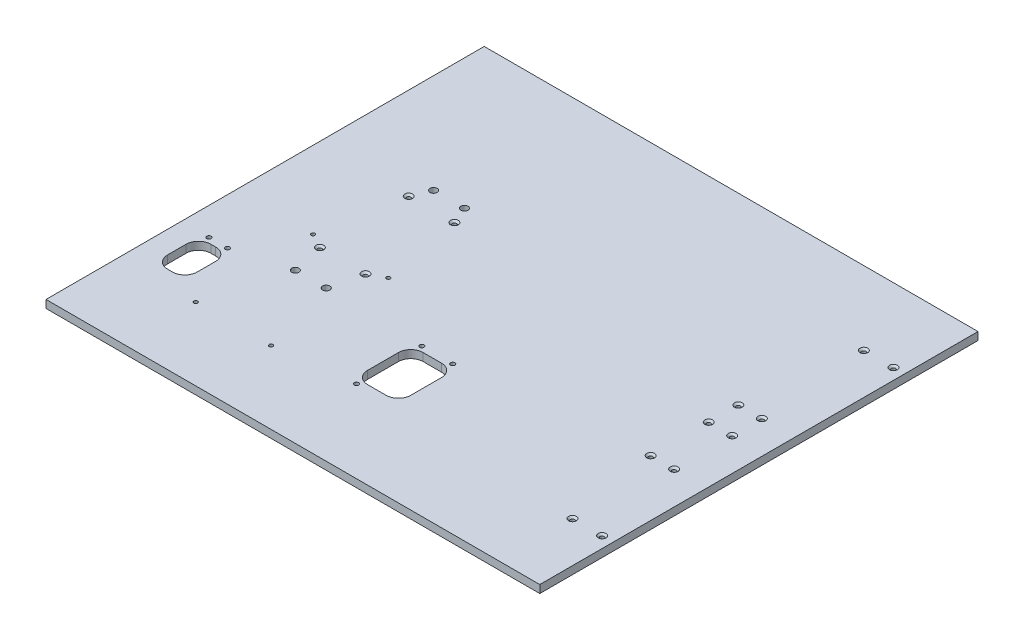
SolidWorks part; units mm, degrees
material "6061-T6 (SS)"
ref_plane "Front Plane" through (0, 0, 0) normal (0, 0, 1) x (1, 0, 0)
ref_plane "Top Plane" through (0, 0, 0) normal (0, 1, 0) x (1, 0, 0)
ref_plane "Right Plane" through (0, 0, 0) normal (1, 0, 0) x (0, 0, -1)
sketch "Sketch1" plane through (0, 0, 0) normal (1, 0, 0) x (0, 0, -1)
  line L1 (-177.5, 0) -> (177.5, 0)
  line L2 (-177.5, -6.35) -> (-177.5, 0)
  line L4 (177.5, -6.35) -> (177.5, 0)
  line L7 (-177.5, -6.35) -> (177.5, -6.35)
  dimension "D1" = 355
  dimension "D2" = 6.35
extrude "Boss-Extrude1" add sketch "Sketch1" along normal mid plane 400
sketch "Sketch9" plane through (0, 0, 0) normal (0, 1, 0) x (1, 0, 0)
  line L4 (200, 0) -> (-200, 0) construction
  line L5 (200, 177.5) -> (200, -177.5) construction
  line L6 (-200, 177.5) -> (-200, -177.5) construction
  line L7 (-125.5, 41.85) -> (-88.5, 41.85) construction
  line L8 (-88.5, 41.85) -> (-88.5, -30.15) construction
  line L9 (-88.5, -30.15) -> (-125.5, -30.15) construction
  line L10 (-125.5, -30.15) -> (-125.5, 41.85) construction
  line L11 (154.5, 28.85) -> (154.5, 4.85) construction
  line L12 (154.5, 4.85) -> (154.5, -42.15) construction
  line L13 (154.5, -42.15) -> (173.5, -42.15) construction
  line L14 (173.5, -42.15) -> (173.5, 4.85) construction
  line L15 (173.5, 4.85) -> (173.5, 28.85) construction
  line L16 (173.5, 28.85) -> (154.5, 28.85) construction
  line L17 (173.5, 4.85) -> (154.5, 4.85) construction
  circle A8 centre (-125.5, 41.85) radius 1.5
  circle A9 centre (-88.5, 41.85) radius 1.5
  circle A10 centre (-125.5, -30.15) radius 1.5
  circle A11 centre (-88.5, -30.15) radius 1.5
  circle A12 centre (154.5, 28.85) radius 1.5
  circle A13 centre (173.5, 4.85) radius 1.5
  circle A14 centre (154.5, 4.85) radius 1.5
  circle A15 centre (173.5, 28.85) radius 1.5
  circle A16 centre (154.5, -42.15) radius 1.5
  circle A17 centre (173.5, -42.15) radius 1.5
  dimension "D1" = 41.85
  dimension "D2" = 72
  dimension "D3" = 37
  dimension "D4" = 74.5
  dimension "D5" = 4.85
  dimension "D6" = 24
  dimension "D7" = 71
  dimension "D8" = 19
  dimension "D9" = 243
extrude "Cut-Extrude8" cut sketch "Sketch9" against normal blind 10
sketch "Sketch19" plane through (0, 0, 0) normal (0, 1, 0) x (1, 0, 0)
  circle A0 centre (-137.5, -23.7) radius 1.5
  circle A2 centre (-76.5, -23.7) radius 1.5
  circle A4 centre (-76.5, -118.7) radius 1.5
  circle A9 centre (-137.5, -118.7) radius 1.5
  dimension "D1" = 3
extrude "Cut-Extrude9" cut sketch "Sketch19" against normal blind 10
hole_wizard "CSK for M3 Flat Head Machine Screw3" positions "Sketch27" profile "Sketch26" countersink size "M3" standard "Ansi Metric"
sketch "Sketch27" plane through (0, 0, 0) normal (0, 1, 0) x (-1, 0, 0)
  point P0 (88.5, -41.85)
  point P7 (125.5, -41.85)
  point P10 (125.5, 30.15)
  point P13 (88.5, 30.15)
  point P22 (-167, 118)
  point P25 (-191, 118)
  point P28 (-154.5, 42.15)
  point P31 (-173.5, 42.15)
  point P34 (-173.5, -4.85)
  point P37 (-154.5, -4.85)
  point P40 (-173.5, -28.85)
  point P43 (-154.5, -28.85)
  point P46 (-191, -118)
  point P49 (-167, -118)
sketch "Sketch26" plane through (-88.5, 0, -41.85) normal (1, 0, 0) x (0, 0, 1)
  line L0 (0, 0) -> (0, 11.0215)
  line L1 (0, 11.0215) -> (1.7, 10)
  line L2 (1.7, 10) -> (1.7, 1.45)
  line L3 (1.7, 1.45) -> (3.15, 0)
  line L5 (3.15, 0) -> (0, 0)
  line L6 (-1.7, 1.45) -> (-3.15, 0) construction
  line L10 (0, 11.0215) -> (-1.7, 10) construction
  line L11 (0, -6.35) -> (0, 107.95) construction
  dimension "Hole Dia." = 3.4
  dimension "Hole Depth" = 10
  dimension "Near C'Sink Dia." = 6.3
  dimension "Near C'Sink Angle" = 90
  dimension "Drill Angle" = 118
sketch "Sketch28" plane through (0, 0, 0) normal (0, 1, 0) x (-1, 0, 0)
  line L1 (10, 62) -> (-5, 62)
  line L2 (20, 72) -> (20, 97)
  line L3 (10, 107) -> (-5, 107)
  line L4 (-15, 72) -> (-15, 97)
  line L5 (200, -177.5) -> (200, 177.5) construction
  line L6 (162.5, 68) -> (177.5, 68) construction
  line L7 (168, 107) -> (172, 107)
  line L8 (158, 97) -> (158, 82)
  line L9 (168, 72) -> (172, 72)
  line L10 (182, 97) -> (182, 82)
  line L11 (170, 68) -> (170, 72) construction
  arc A0 (-5, 107) -> (-15, 97) centre (-5, 97) ccw
  arc A1 (-5, 62) -> (-15, 72) centre (-5, 72) cw
  arc A2 (10, 62) -> (20, 72) centre (10, 72) ccw
  arc A3 (20, 97) -> (10, 107) centre (10, 97) ccw
  circle A4 centre (15, 111) radius 1.75
  arc A5 (172, 72) -> (182, 82) centre (172, 82) ccw
  arc A6 (158, 82) -> (168, 72) centre (168, 82) ccw
  arc A7 (168, 107) -> (158, 97) centre (168, 97) ccw
  arc A8 (172, 107) -> (182, 97) centre (172, 97) cw
  circle A9 centre (15, 58) radius 1.75
  circle A10 centre (-10, 58) radius 1.75
  circle A11 centre (162.5, 68) radius 1.75
  circle A12 centre (177.5, 68) radius 1.75
  dimension "D5" = 10
  dimension "D6" = 4
  dimension "D8" = 5
  dimension "D9" = 10
  dimension "D14" = 3.5
  dimension "D2" = 45
  dimension "D3" = 180
  dimension "D4" = 215
  dimension "D7" = 4
  dimension "D10" = 18
  dimension "D12" = 24
  dimension "D13" = 35
  dimension "D15" = 5
  dimension "D16" = 15
  dimension "D17" = 4
extrude "Cut-Extrude11" cut sketch "Sketch28" against normal blind 10
hole_wizard "M5 Clearance Hole1" positions "Sketch32" profile "Sketch29" hole size "M5" standard "ANSI Metric" end condition through all
sketch "Sketch32" plane through (0, 0, 0) normal (0, 1, 0) x (1, 0, 0)
  line L0 (-200, 0) -> (200, 0) construction
  line L1 (-200, 177.5) -> (-200, -177.5) construction
  line L2 (200, 177.5) -> (200, -177.5) construction
  line L4 (-94.5, 56) -> (-94.5, -56) construction
  line L5 (-94.5, -56) -> (-119.5, -56) construction
  line L6 (-119.5, -56) -> (-119.5, 56) construction
  line L7 (-119.5, 56) -> (-94.5, 56) construction
  line L9 (-107, 56) -> (-107, -56) construction
  point P0 (-119.5, 56)
  point P2 (-94.5, 56)
  point P4 (-94.5, -56)
  point P6 (-119.5, -56)
  dimension "D1" = 56
  dimension "D2" = 112
  dimension "D3" = 25
  dimension "D4" = 93
sketch "Sketch29" plane through (-119.5, 0, -56) normal (1, 0, 0) x (0, 0, 1)
  line L0 (0, 0) -> (0, 6.35)
  line L1 (0, 6.35) -> (2.9, 6.35)
  line L2 (2.9, 6.35) -> (2.9, 0)
  line L5 (2.9, 0) -> (0, 0)
  line L11 (0, -6.35) -> (0, 107.95) construction
  dimension "Thru Hole Dia." = 5.8
  dimension "Thru Hole Depth" = 6.35
